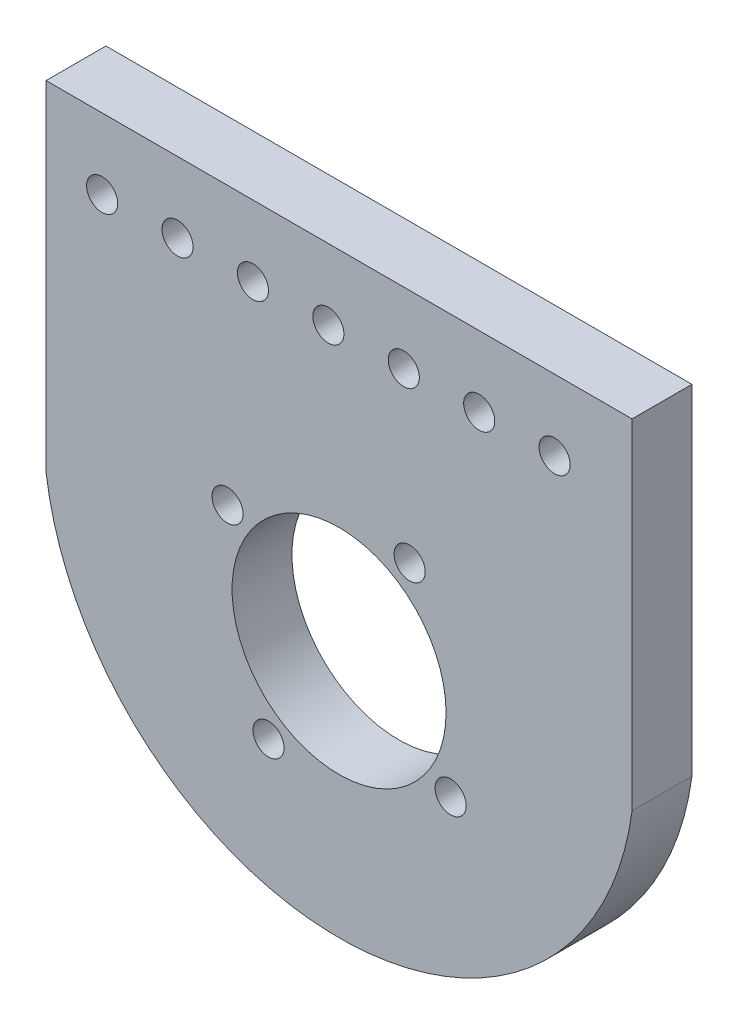
SolidWorks part; units mm, degrees
ref_plane "Front" through (0, 0, 0) normal (0, 0, 1) x (1, 0, 0)
ref_plane "Top" through (0, 0, 0) normal (0, 1, 0) x (1, 0, 0)
ref_plane "Right" through (0, 0, 0) normal (1, 0, 0) x (0, 0, -1)
sketch "Sketch1" plane through (0, 0, 0) normal (0, 0, 1) x (1, 0, 0)
  line L0 (-31.0822, 36.8639) -> (31.0822, 36.8639)
  line L1 (-31.0822, 36.8639) -> (-31.0822, 0.8639)
  line L2 (31.0822, 36.8639) -> (31.0822, 0.8639)
  line L3 (-31.0822, 29.3639) -> (31.0822, 29.3639) construction
  line L4 (-23.0822, 29.3639) -> (39.0822, 29.3639) construction
  line L5 (-15.0822, 29.3639) -> (47.0822, 29.3639) construction
  line L6 (-7.0822, 29.3639) -> (55.0822, 29.3639) construction
  line L7 (0.9178, 29.3639) -> (63.0822, 29.3639) construction
  line L8 (8.9178, 29.3639) -> (71.0822, 29.3639) construction
  line L9 (16.9178, 29.3639) -> (79.0822, 29.3639) construction
  circle A0 centre (0, 0) radius 11.35
  arc A1 (-31.0822, 0.8639) -> (31.0822, 0.8639) centre (0, 5) ccw
  circle A2 centre (0, 0) radius 14 construction
  circle A3 centre (-11.832, 7.4835) radius 1.65
  circle A4 centre (7.4835, 11.832) radius 1.65
  circle A5 centre (11.832, -7.4835) radius 1.65
  circle A6 centre (-7.4835, -11.832) radius 1.65
  circle A7 centre (-25.1356, 29.3639) radius 1.65
  circle A8 centre (-17.1356, 29.3639) radius 1.65
  circle A9 centre (-9.1356, 29.3639) radius 1.65
  circle A10 centre (-1.1356, 29.3639) radius 1.65
  circle A11 centre (6.8644, 29.3639) radius 1.65
  circle A12 centre (14.8644, 29.3639) radius 1.65
  circle A13 centre (22.8644, 29.3639) radius 1.65
  point P6 (0, 36.8639)
  point P21 (0, 0)
  dimension "D1" = 22.7
  dimension "D2" = 28
  dimension "D3" = 3.3
  dimension "D5" = 5
  dimension "D6" = 5
  dimension "D9" = 3.3
  dimension "D7" = 36
  dimension "D8" = 7.5
  dimension "D11" = 8
  dimension "D10" = 7
  dimension "D4" = 4
extrude "Boss-Extrude1" add sketch "Sketch1" along normal blind 6.35
